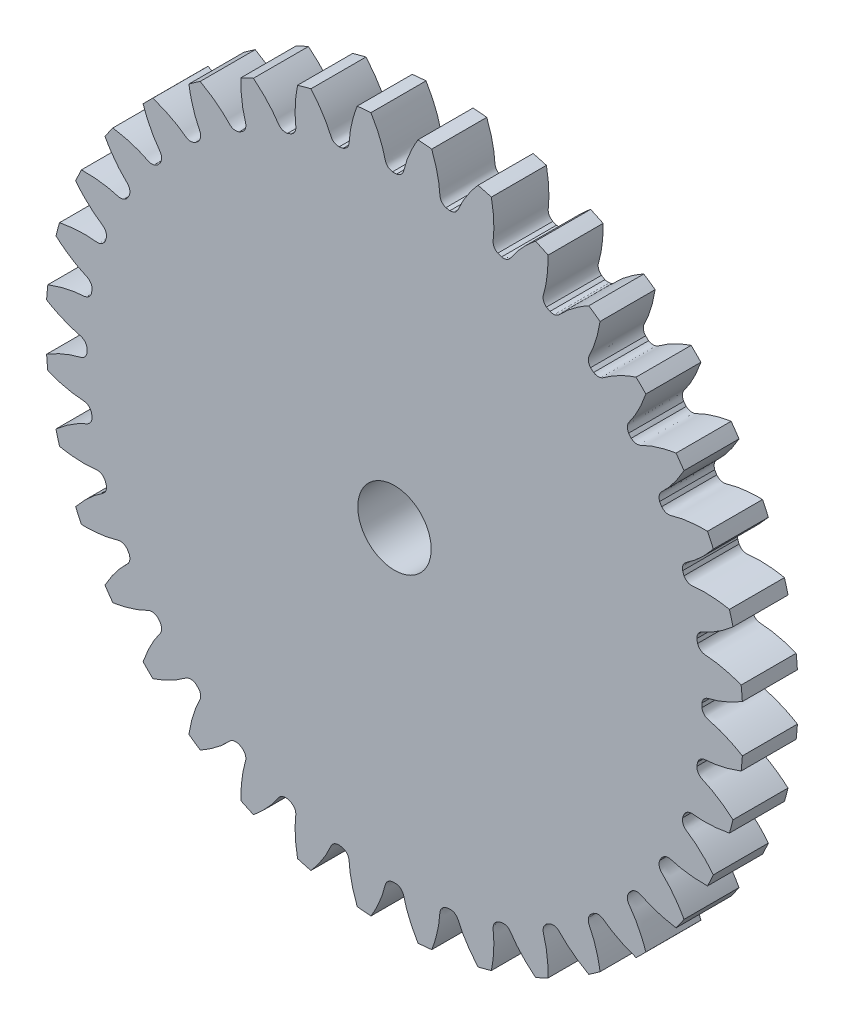
SolidWorks part; units mm, degrees
material "A286 铁基超合金"
ref_plane "前视基准面" through (0, 0, 0) normal (0, 0, 1) x (1, 0, 0)
ref_plane "上视基准面" through (0, 0, 0) normal (0, 1, 0) x (1, 0, 0)
ref_plane "右视基准面" through (0, 0, 0) normal (1, 0, 0) x (0, 0, -1)
sketch "草图1" plane through (0, 0, 0) normal (0, 0, 1) x (1, 0, 0)
  circle A0 centre (0, 0) radius 9.5
extrude "凸台-拉伸1" add sketch "草图1" against normal blind 1.5
ref_axis "基准轴1" through (0, 0, 0) along (0, 0, -1)
sketch "草图2" plane through (0, 0, 0) normal (0, 0, 1) x (1, 0, 0)
  line L0 (0, 0) -> (0, 9.5) construction
  circle A0 centre (0, 0) radius 9.5 construction
  arc A1 (0.0549, 8.3748) -> (-0.0549, 8.3748) centre (0, 0) ccw
  arc A2 (1.757, 10.7884) -> (-1.757, 10.7884) centre (0, 0) ccw
  spline S0 degree 3 poles (0.0549, 8.3748) (0.235, 8.4152) (0.2505, 8.5493) (0.2882, 8.6914) (0.2997, 8.7319) (0.3131, 8.7753) (0.3284, 8.8217) (0.3457, 8.871) (0.3652, 8.9231) (0.3869, 8.9779) (0.4111, 9.0354) (0.4378, 9.0956) (0.4671, 9.1582) (0.4992, 9.2232) (0.5341, 9.2907) (0.5719, 9.3603) (0.6128, 9.4322) (0.6569, 9.5061) (0.7043, 9.582) (0.755, 9.6598) (0.8091, 9.7393) (0.8668, 9.8205) (0.9281, 9.9032) (0.9931, 9.9874) (1.0619, 10.0729) (1.1346, 10.1596) (1.2112, 10.2474) (1.2919, 10.3361) (1.3766, 10.4256) (1.4655, 10.5159) (1.5912, 10.6386) (1.6895, 10.7288) (1.757, 10.7884) knots 0 0 0 0 0.120371 0.133303 0.147364 0.162556 0.178878 0.19633 0.214913 0.234626 0.255469 0.277443 0.300547 0.324782 0.350146 0.376641 0.404267 0.433023 0.462909 0.493925 0.526072 0.559349 0.593757 0.629294 0.665963 0.703761 0.74269 0.782749 0.823939 0.866258 0.909709 1 1 1 1
  spline S1 degree 3 poles (-0.0549, 8.3748) (-0.235, 8.4152) (-0.2505, 8.5493) (-0.2882, 8.6914) (-0.2997, 8.7319) (-0.3131, 8.7753) (-0.3284, 8.8217) (-0.3457, 8.871) (-0.3652, 8.9231) (-0.3869, 8.9779) (-0.4111, 9.0354) (-0.4378, 9.0956) (-0.4671, 9.1582) (-0.4992, 9.2232) (-0.5341, 9.2907) (-0.5719, 9.3603) (-0.6128, 9.4322) (-0.6569, 9.5061) (-0.7043, 9.582) (-0.755, 9.6598) (-0.8091, 9.7393) (-0.8668, 9.8205) (-0.9281, 9.9032) (-0.9931, 9.9874) (-1.0619, 10.0729) (-1.1346, 10.1596) (-1.2112, 10.2474) (-1.2919, 10.3361) (-1.3766, 10.4256) (-1.4655, 10.5159) (-1.5912, 10.6386) (-1.6895, 10.7288) (-1.757, 10.7884) knots 0 0 0 0 0.120371 0.133303 0.147364 0.162556 0.178878 0.19633 0.214913 0.234626 0.255469 0.277443 0.300547 0.324782 0.350146 0.376641 0.404267 0.433023 0.462909 0.493925 0.526072 0.559349 0.593757 0.629294 0.665963 0.703761 0.74269 0.782749 0.823939 0.866258 0.909709 1 1 1 1
extrude "切除-拉伸1" cut sketch "草图2" against normal through all
pattern_circular "阵列(圆周)1" count 36 over 360 about axis through (0, 0, 0) along (0, 0, -1) of "切除-拉伸1"
sketch "草图3" plane through (0, 0, 0) normal (0, 0, 1) x (1, 0, 0)
  circle A0 centre (0, 0) radius 9 construction
  dimension "Dn" = 18
sketch "草图4" plane through (0, 0, 0) normal (0, 0, 1) x (1, 0, 0)
  circle A0 centre (0, 0) radius 1
extrude "切除-拉伸2" cut sketch "草图4" against normal through all
sketch "草图5" plane through (0, 0, 0) normal (0, 0, 1) x (1, 0, 0)
  line L0 (8.375, 0) -> (0, 0) construction
  arc A0 (8.3748, -0.0549) -> (8.3748, 0.0549) centre (0, 0) ccw construction
